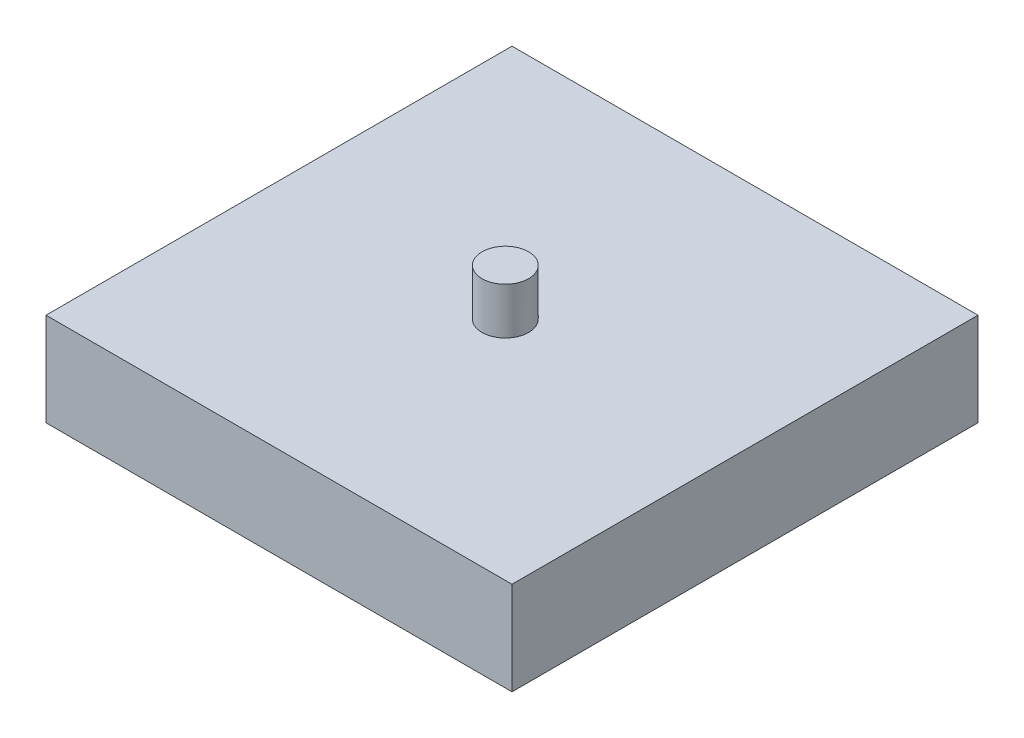
SolidWorks part; units mm, degrees
ref_plane "Front Plane" through (0, 0, 0) normal (0, 0, 1) x (1, 0, 0)
ref_plane "Top Plane" through (0, 0, 0) normal (0, 1, 0) x (1, 0, 0)
ref_plane "Right Plane" through (0, 0, 0) normal (1, 0, 0) x (0, 0, -1)
sketch "Sketch2" plane through (0, 0, 0) normal (0, 1, 0) x (1, 0, 0)
  line L0 (0, 0) -> (0, 658.0357) construction
  line L1 (-250, 257.1511) -> (250, 257.1511)
  line L2 (-250, 257.1511) -> (-250, -242.8489)
  line L3 (-250, -242.8489) -> (250, -242.8489)
  line L4 (250, 257.1511) -> (250, -242.8489)
  circle A0 centre (0, 0) radius 25
  point P6 (0, 257.1511)
  dimension "D3" = 50
  dimension "D1" = 500
  dimension "D2" = 500
extrude "Boss-Extrude1" add sketch "Sketch2" along normal blind 100 contours L2 L3 L4 L1
sketch "Sketch3" plane through (0, 100, 0) normal (0, 1, 0) x (1, 0, 0)
  line L0 (0, 0) -> (0, -773.5293) construction
  line L2 (-194.1834, -377.2403) -> (-192.2742, -377.2403)
  line L4 (-194.1834, -556.4135) -> (-192.2742, -556.4135)
  line L6 (194.1834, -377.2403) -> (192.2742, -377.2403)
  line L8 (194.1834, -556.4135) -> (192.2742, -556.4135)
extrude "Boss-Extrude2" add sketch "Sketch3" along normal blind 200 rebuild error yes
sketch "Sketch4" plane through (0, 100, 0) normal (0, 1, 0) x (1, 0, 0)
  circle A0 centre (0, 0) radius 25
  dimension "D1" = 50
extrude "Boss-Extrude3" add sketch "Sketch4" along normal blind 50
